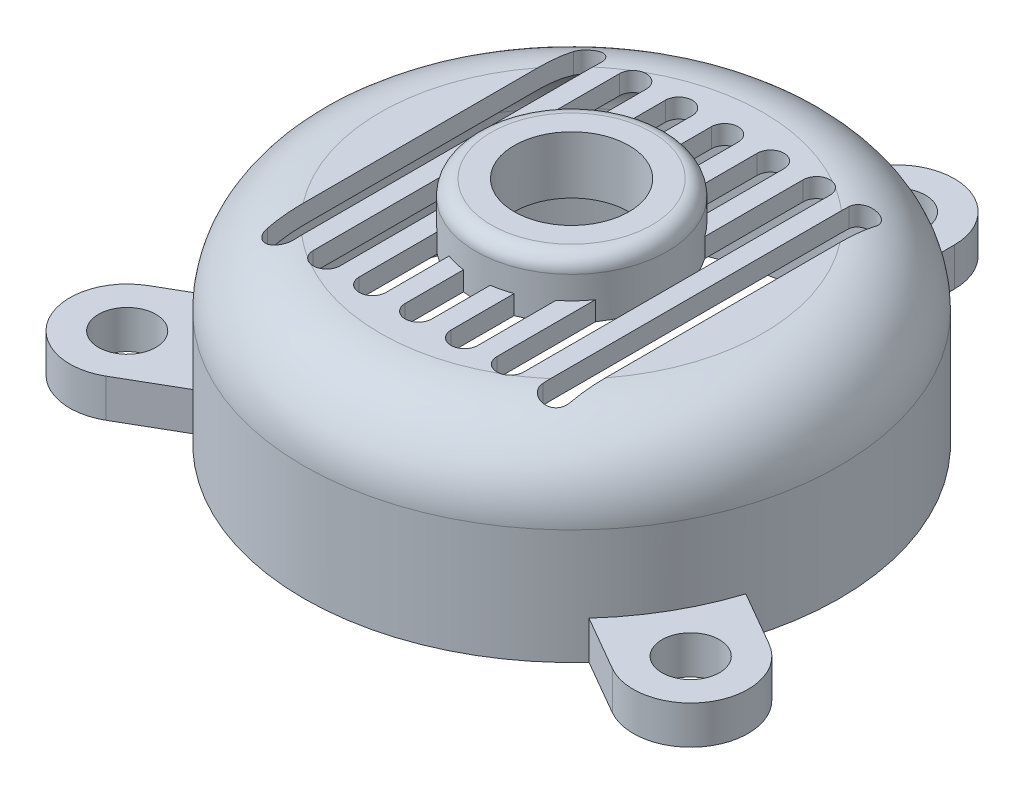
SolidWorks part; units mm, degrees
ref_plane "Front Plane" through (0, 0, 0) normal (0, 0, 1) x (1, 0, 0)
ref_plane "Top Plane" through (0, 0, 0) normal (0, 1, 0) x (1, 0, 0)
ref_plane "Right Plane" through (0, 0, 0) normal (1, 0, 0) x (0, 0, -1)
sketch "Sketch1" plane through (0, 0, 0) normal (0, 1, 0) x (1, 0, 0)
  line L0 (0, 0) -> (-30221.1505, 0) construction
  line L1 (0, 0) -> (0, -30221.1505) construction
  line L2 (7.5, 42.5) -> (7.5, 34.187)
  line L3 (-7.5, 42.5) -> (-7.5, 34.187)
  line L4 (33.0561, -27.7452) -> (25.8568, -23.5887)
  line L5 (40.5561, -14.7548) -> (33.3568, -10.5983)
  line L6 (-40.5561, -14.7548) -> (-33.3568, -10.5983)
  line L7 (-33.0561, -27.7452) -> (-25.8568, -23.5887)
  arc A0 (-7.5, 34.187) -> (7.5, 34.187) centre (0, 0) ccw
  circle A1 centre (0, 0) radius 42.5 construction
  circle A2 centre (0, 42.5) radius 3.75
  arc A3 (7.5, 42.5) -> (-7.5, 42.5) centre (0, 42.5) ccw
  circle A4 centre (36.8061, -21.25) radius 3.75
  arc A5 (33.0561, -27.7452) -> (40.5561, -14.7548) centre (36.8061, -21.25) ccw
  circle A6 centre (-36.8061, -21.25) radius 3.75
  arc A7 (-40.5561, -14.7548) -> (-33.0561, -27.7452) centre (-36.8061, -21.25) ccw
  arc A8 (-7.5, 34.187) -> (7.5, 34.187) centre (0, 0) cw
  point P27 (0, 0)
  dimension "D1" = 70
  dimension "D2" = 85
  dimension "D3" = 7.5
  dimension "D4" = 15
  dimension "D6" = 35
  dimension "D5" = 3
extrude "Boss-Extrude1" add sketch "Sketch1" along normal blind 25 contours A8 A0 region at (0, 0, 0)
fillet "Fillet1" radius 10 1 edges at (0, 25, 35)
shell "Shell1" thickness 2.5 removed face at (0, 0, 35)
extrude "Boss-Extrude2" add sketch "Sketch1<3>" along normal blind 5 contours L4 A5 L5 A0 A4 | L6 A7 L7 A0 A6 | L3 A8 L2 A3 A2 region at (7.282, 0, -38.3435) region at (36.827, 0, 12.9007) region at (-30.535, 0, 17.6294)
sketch "Sketch1<3>" plane through (0, 0, 0) normal (0, 1, 0) x (1, 0, 0) same geometry as "Sketch1"
sketch "Sketch2" plane through (0, 0, 0) normal (0, -1, 0) x (1, 0, 0)
  line L0 (0, 0) -> (-50000, 0) construction
  line L1 (0, 0) -> (0, -50000) construction
  line L2 (-10.25, 20) -> (-10.25, -20)
  line L4 (-19.75, 20) -> (-19.75, -20)
  line L6 (-16.25, 20) -> (-16.25, -20)
  line L7 (-18, -20) -> (-18, 20) construction
  line L8 (-19.75, 0) -> (-16.25, 0) construction
  line L9 (-13.75, 20) -> (-13.75, -20)
  line L10 (-4.25, 20) -> (-4.25, -20)
  line L11 (-7.75, 20) -> (-7.75, -20)
  line L12 (1.75, 20) -> (1.75, -20)
  line L13 (-1.75, 20) -> (-1.75, -20)
  line L14 (7.75, 20) -> (7.75, -20)
  line L15 (4.25, 20) -> (4.25, -20)
  line L16 (13.75, 20) -> (13.75, -20)
  line L17 (10.25, 20) -> (10.25, -20)
  line L18 (19.75, 20) -> (19.75, -20)
  line L19 (16.25, 20) -> (16.25, -20)
  arc A0 (-19.75, -20) -> (-16.25, -20) centre (-18, -20) ccw
  arc A1 (-16.25, 20) -> (-19.75, 20) centre (-18, 20) ccw
  arc A2 (-13.75, -20) -> (-10.25, -20) centre (-12, -20) ccw
  arc A3 (-10.25, 20) -> (-13.75, 20) centre (-12, 20) ccw
  arc A4 (-7.75, -20) -> (-4.25, -20) centre (-6, -20) ccw
  arc A5 (-4.25, 20) -> (-7.75, 20) centre (-6, 20) ccw
  arc A6 (-1.75, -20) -> (1.75, -20) centre (0, -20) ccw
  arc A7 (1.75, 20) -> (-1.75, 20) centre (0, 20) ccw
  arc A8 (4.25, -20) -> (7.75, -20) centre (6, -20) ccw
  arc A9 (7.75, 20) -> (4.25, 20) centre (6, 20) ccw
  arc A10 (10.25, -20) -> (13.75, -20) centre (12, -20) ccw
  arc A11 (13.75, 20) -> (10.25, 20) centre (12, 20) ccw
  arc A12 (16.25, -20) -> (19.75, -20) centre (18, -20) ccw
  arc A13 (19.75, 20) -> (16.25, 20) centre (18, 20) ccw
  point P5 (-18, 0)
  dimension "D4" = 1.75
  dimension "D1" = 3.5
  dimension "D2" = 40
  dimension "D3" = 18
  dimension "D6" = 6
  dimension "D5" = 7
extrude "Cut-Extrude1" cut sketch "Sketch2" against normal blind 35
sketch "Sketch4" plane through (0, 22.5, 0) normal (0, -1, 0) x (1, 0, 0)
  circle A0 centre (0, 0) radius 7.5
  circle A1 centre (0, 0) radius 12.5
  dimension "D1" = 15
  dimension "D2" = 25
extrude "Boss-Extrude3" add sketch "Sketch4" against normal blind 7.5 contours A0 | A1 A0 region at (0, 22.5, 0) region at (-12.1464, 22.5, 0)
extrude "Cut-Extrude2" cut sketch "Sketch4<3>" against normal mid plane 37.5 contours A0 region at (0, 22.5, 0)
sketch "Sketch4<3>" plane through (0, 22.5, 0) normal (0, -1, 0) x (1, 0, 0) same geometry as "Sketch4"
fillet "Fillet2" radius 2 1 edges at (0, 30, -12.5)
